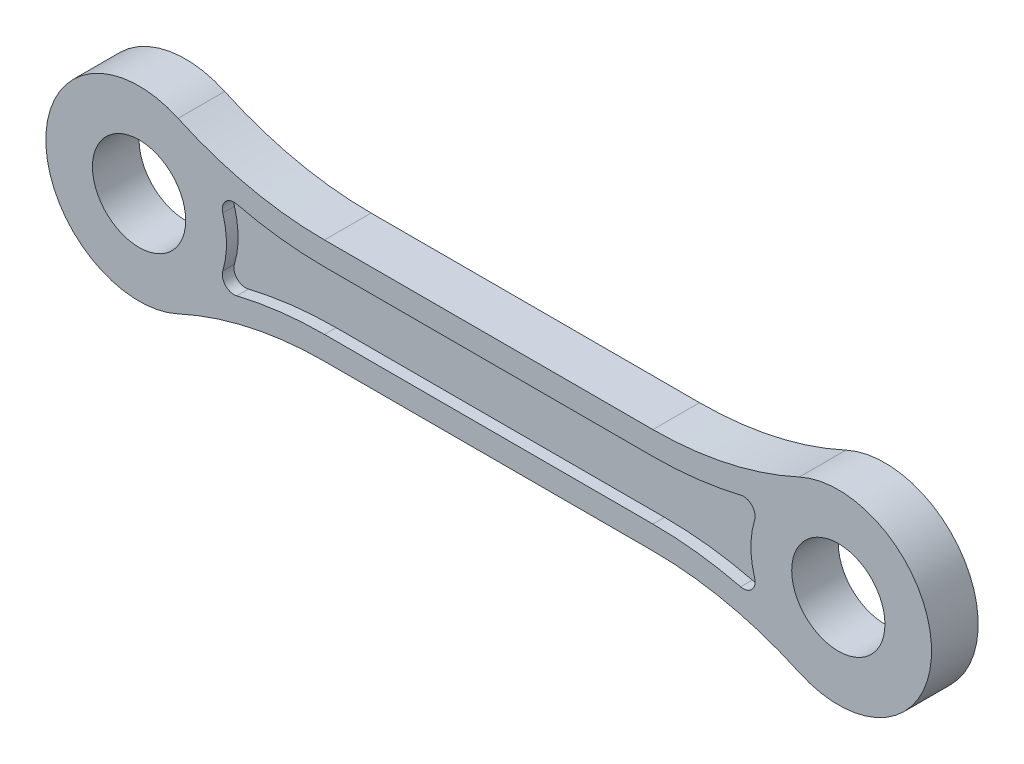
SolidWorks part; units mm, degrees
material "6061 合金"
ref_plane "前视基准面" through (0, 0, 0) normal (0, 0, 1) x (1, 0, 0)
ref_plane "上视基准面" through (0, 0, 0) normal (0, 1, 0) x (1, 0, 0)
ref_plane "右视基准面" through (0, 0, 0) normal (1, 0, 0) x (0, 0, -1)
other "Configuration Table"
sketch "草图1" plane through (0, 0, 0) normal (0, 0, 1) x (1, 0, 0)
  line L0 (-30, 0) -> (30, 0) construction
  line L1 (-30, 8) -> (30, 8)
  line L2 (-30, -8) -> (30, -8)
  arc A0 (-30, 8) -> (-30, -8) centre (-30, 0) ccw
  arc A1 (30, -8) -> (30, 8) centre (30, 0) ccw
  circle A2 centre (-30, 0) radius 4
  circle A3 centre (30, 0) radius 4
  point P2 (0, 0)
  dimension "D2" = 8
  dimension "D3" = 8
  dimension "D4" = 8
  dimension "D1" = 60
extrude "凸台-拉伸1" add sketch "草图1" along normal blind 4
sketch "草图2" plane through (0, 0, 4) normal (0, 0, 1) x (1, 0, 0)
  line L0 (-30, 0) -> (49970, 0) construction
  line L1 (-14.0914, -4.5097) -> (14.0914, -4.5097)
  line L2 (-14.0914, 4.5097) -> (14.0914, 4.5097)
  line L4 (-23.0416, -3.9472) -> (23.0416, -3.9472)
  line L6 (-24.2525, 4.1546) -> (23.0416, -3.9472) construction
  line L7 (-23.0416, -3.9472) -> (23.5601, 4.036) construction
  line L9 (-30, -8) -> (30, -8)
  line L10 (30, 8) -> (-30, 8)
  line L11 (-30, -8) -> (30, -8)
  line L12 (30, 8) -> (-30, 8)
  arc A0 (-26.6508, 7.2652) -> (-23.0416, -3.9472) centre (-30, 0) ccw
  arc A1 (23.0416, -3.9472) -> (26.6508, 7.2652) centre (30, 0) ccw
  arc A2 (14.0914, 4.5097) -> (26.6508, 7.2652) centre (14.0914, 34.5097) ccw
  arc A3 (-14.0914, 4.5097) -> (-26.6508, 7.2652) centre (-14.0914, 34.5097) cw
  arc A4 (-30, 8) -> (-30, -8) centre (-30, 0) ccw
  arc A5 (30, -8) -> (30, 8) centre (30, 0) ccw
  arc A6 (-30, 8) -> (-30, -8) centre (-30, 0) ccw
  arc A7 (30, -8) -> (30, 8) centre (30, 0) ccw
  arc A8 (14.0914, -4.5097) -> (26.6508, -7.2652) centre (14.0914, -34.5097) cw
  arc A9 (-14.0914, -4.5097) -> (-26.6508, -7.2652) centre (-14.0914, -34.5097) ccw
  point P7 (0, 0)
  line M5 (-30, -8) -> (30, -8)
  line M7 (30, 8) -> (-30, 8)
  dimension "D3" = 30
  dimension "D4" = 8
  dimension "D1" = 8
  dimension "D2" = 0
extrude "切除-拉伸1" cut sketch "草图2" against normal blind 10 contours A3 L2 A2 A1 A0 M7 | L1 A9 A0 A1 A8 M5
sketch "草图3" plane through (0, 0, 4) normal (0, 0, 1) x (1, 0, 0)
  line L6 (-14.0914, -2.5097) -> (14.3209, -2.5097)
  line L7 (14.0914, 2.5097) -> (-14.0914, 2.5097)
  line L8 (-14.0914, -4.5097) -> (14.0914, -4.5097)
  line L9 (14.0914, 4.5097) -> (-14.0914, 4.5097)
  line L10 (-14.0914, -4.5097) -> (14.0914, -4.5097)
  line L11 (14.0914, 4.5097) -> (-14.0914, 4.5097)
  arc A21 (28.7083, -5.8593) -> (27.4881, 5.4489) centre (30, 0) ccw
  arc A22 (14.0914, 2.5097) -> (27.4881, 5.4489) centre (14.0914, 34.5097) ccw
  arc A23 (-27.4881, 5.4489) -> (-14.0914, 2.5097) centre (-14.0914, 34.5097) ccw
  arc A24 (-27.4881, 5.4489) -> (-27.4881, -5.4489) centre (-30, 0) ccw
  arc A25 (-14.0914, -2.5097) -> (-27.4881, -5.4489) centre (-14.0914, -34.5097) ccw
  arc A26 (-26.6508, 7.2652) -> (-14.0914, 4.5097) centre (-14.0914, 34.5097) ccw
  arc A27 (-26.6508, 7.2652) -> (-26.6508, -7.2652) centre (-30, 0) ccw
  arc A28 (-14.0914, -4.5097) -> (-26.6508, -7.2652) centre (-14.0914, -34.5097) ccw
  arc A30 (-26.6508, 7.2652) -> (-26.6508, -7.2652) centre (-30, 0) ccw
  arc A31 (14.0914, 4.5097) -> (26.6508, 7.2652) centre (14.0914, 34.5097) ccw
  arc A32 (-26.6508, 7.2652) -> (-14.0914, 4.5097) centre (-14.0914, 34.5097) ccw
  arc A34 (-14.0914, -4.5097) -> (-26.6508, -7.2652) centre (-14.0914, -34.5097) ccw
  arc A37 (14.0914, 4.5097) -> (26.6508, 7.2652) centre (14.0914, 34.5097) ccw
  circle A38 centre (-30, 0) radius 7.5
  circle A39 centre (30, 0) radius 7.5
  arc A40 (28.7083, -5.8593) -> (27.4881, 5.4489) centre (30, 0) ccw construction
  arc A41 (27.4881, -5.4489) -> (14.0914, -2.5097) centre (14.0914, -34.5097) ccw
  arc A45 (-26.6508, 7.2652) -> (-26.6508, -7.2652) centre (-30, 0) ccw construction
  arc A46 (28.2651, -7.8096) -> (14.0914, -4.5097) centre (-6301.8961, -27164.5106) ccw construction
  arc A47 (28.2651, -7.8096) -> (26.6508, 7.2652) centre (30, 0) ccw construction
  arc A50 (26.6508, -7.2652) -> (14.0914, -4.5097) centre (14.0914, -34.5097) ccw
  arc A51 (26.6508, -7.2652) -> (14.0914, -4.5097) centre (14.0914, -34.5097) ccw
  arc A52 (26.6508, -7.2652) -> (26.6508, 7.2652) centre (30, 0) ccw
  arc A53 (26.6508, -7.2652) -> (26.6508, 7.2652) centre (30, 0) ccw
  arc A54 (28.7083, -5.8593) -> (14.3209, -2.5097) centre (-6301.8961, -27164.5106) ccw construction
  point P9 (0, 0)
  point P15 (30.1805, 0)
  point P16 (28.8862, -5.8957)
  point P30 (-29.6367, 0)
  point P38 (30, -6)
  point P39 (28.7083, -5.8593)
  dimension "D1" = 0
  dimension "D2" = 2
  dimension "D3" = 2
extrude "切除-拉伸2" cut sketch "草图3" against normal blind 1
ref_plane "基准面1" through (0, 0, 2) normal (0, 0, -1) x (-1, 0, 0)
fillet "圆角1" radius 1 4 edges at (-23.6342, -3.9657, 3.5) (-23.6342, 3.9657, 3.5) (23.6342, 3.9657, 3.5) (23.6342, -3.9657, 3.5)
sketch "草图5" plane through (0, 0, 0) normal (0, 0, -1) x (-1, 0, 0)
  circle A0 centre (30, 0) radius 7.5
  circle A1 centre (30, 0) radius 4
  circle A2 centre (-30, 0) radius 4
  circle A3 centre (-30, 0) radius 7.5
extrude "凸台-拉伸2" add sketch "草图5" along normal blind 0.25
mirror "镜向1" about plane through (0, 0, 2) normal (0, 0, -1) of "圆角1", "切除-拉伸2"
sketch "草图4" plane through (0, 0, -0.25) normal (0, 0, 1) x (1, 0, 0)
  circle A0 centre (30, 0) radius 7
  circle A1 centre (-30, 0) radius 5
  circle A2 centre (-30, 0) radius 7
  circle A3 centre (30, 0) radius 5
  dimension "D1" = 14
  dimension "D2" = 10
  dimension "D3" = 14
  dimension "D4" = 10
extrude "切除-拉伸3" cut sketch "草图4" along normal blind 1
fillet "圆角2" radius 1 4 edges at (-23, 0, 0.75) (-25, 0, 0.75) (35, 0, 0.75) (37, 0, 0.75)
sketch "草图6" plane through (0, 0, -0.25) normal (0, 0, -1) x (-1, 0, 0)
  circle A0 centre (30, 0) radius 7.5
  circle A1 centre (-30, 0) radius 7.5
extrude "切除-拉伸4" cut sketch "草图6" against normal blind 0.25
